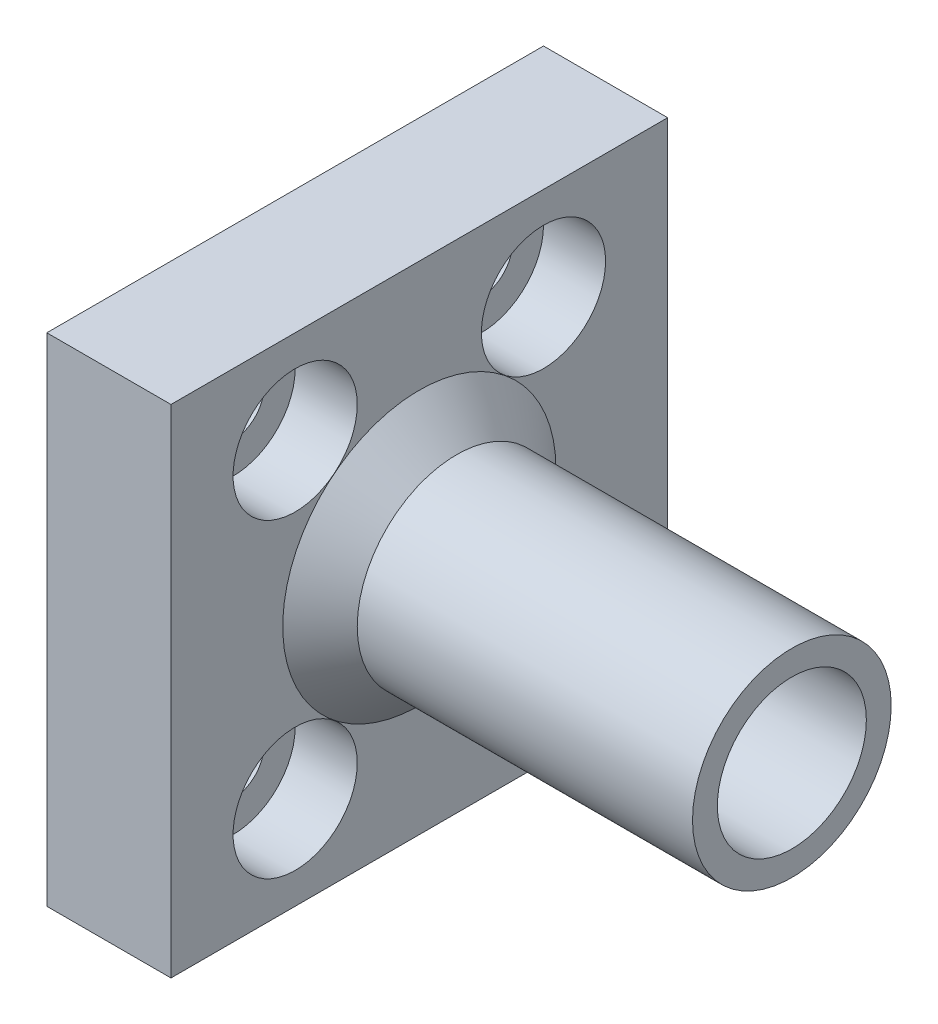
SolidWorks part; units mm, degrees
ref_plane "Front Plane" through (0, 0, 0) normal (0, 0, 1) x (1, 0, 0)
ref_plane "Top Plane" through (0, 0, 0) normal (0, 1, 0) x (1, 0, 0)
ref_plane "Right Plane" through (0, 0, 0) normal (1, 0, 0) x (0, 0, -1)
other "Configuration Table"
sketch "Sketch1" plane through (0, 0, 0) normal (1, 0, 0) x (0, 0, -1)
  line L1 (20, -20) -> (-20, -20)
  line L2 (20, -20) -> (20, 20)
  line L3 (20, 20) -> (-20, 20)
  line L4 (-20, -20) -> (-20, 20)
  line L5 (20, -20) -> (-20, 20) construction
  line L6 (20, 20) -> (-20, -20) construction
  point P0 (0, 0)
  dimension "D1" = 40
  dimension "D2" = 40
extrude "Boss-Extrude1" add sketch "Sketch1" along normal blind 10
sketch "Sketch2" plane through (10, 0, 0) normal (1, 0, 0) x (0, 0, -1)
  circle A0 centre (0, 0) radius 8
extrude "Boss-Extrude2" add sketch "Sketch2" along normal blind 30
sketch "Sketch3" plane through (10, 0, 0) normal (1, 0, 0) x (0, 0, -1)
  line L0 (-10, -20) -> (-10, 20) construction
  line L1 (-20, -20) -> (20, -20) construction
  line L2 (20, 20) -> (-20, 20) construction
  line L3 (10, -20) -> (10, 20) construction
  dimension "D1" = 10
  dimension "D2" = 10
sketch "Sketch4" plane through (10, 0, 0) normal (1, 0, 0) x (0, 0, -1)
  line L0 (-10, -20) -> (-10, 20) construction
  line L1 (10, -20) -> (10, 20) construction
  circle A0 centre (-10, 12.5) radius 2.5
  circle A1 centre (-10, -12.5) radius 2.5
  circle A2 centre (10, 12.5) radius 2.5
  circle A3 centre (10, -12.5) radius 2.5
  point P14 (0, 0)
  point P16 (0, 0)
  dimension "D1" = 12.5
  dimension "D2" = 12.5
extrude "Cut-Extrude1" cut sketch "Sketch4" against normal through all
sketch "Sketch5" plane through (40, 0, 0) normal (1, 0, 0) x (0, 0, -1)
  circle A0 centre (0, 0) radius 6
extrude "Cut-Extrude2" cut sketch "Sketch5" against normal blind 34
sketch "Sketch6" plane through (10, 0, 0) normal (1, 0, 0) x (0, 0, -1)
  circle A0 centre (-10, 12.5) radius 5
  circle A1 centre (10, 12.5) radius 5
  circle A2 centre (10, -12.5) radius 5
  circle A3 centre (-10, -12.5) radius 5
extrude "Cut-Extrude3" cut sketch "Sketch6" against normal blind 5
sketch "Sketch7" plane through (6, 0, 0) normal (1, 0, 0) x (0, 0, -1)
  circle A0 centre (0, 0) radius 1
extrude "Cut-Extrude4" cut sketch "Sketch7" against normal through all
sketch "Sketch8" plane through (0, 0, 0) normal (-1, 0, 0) x (0, 0, 1)
  circle A0 centre (0, 0) radius 2.5
extrude "Cut-Extrude5" cut sketch "Sketch8" against normal blind 3
chamfer "Chamfer1" distance 3 angle 45 1 edges at (10, 0, -8)
